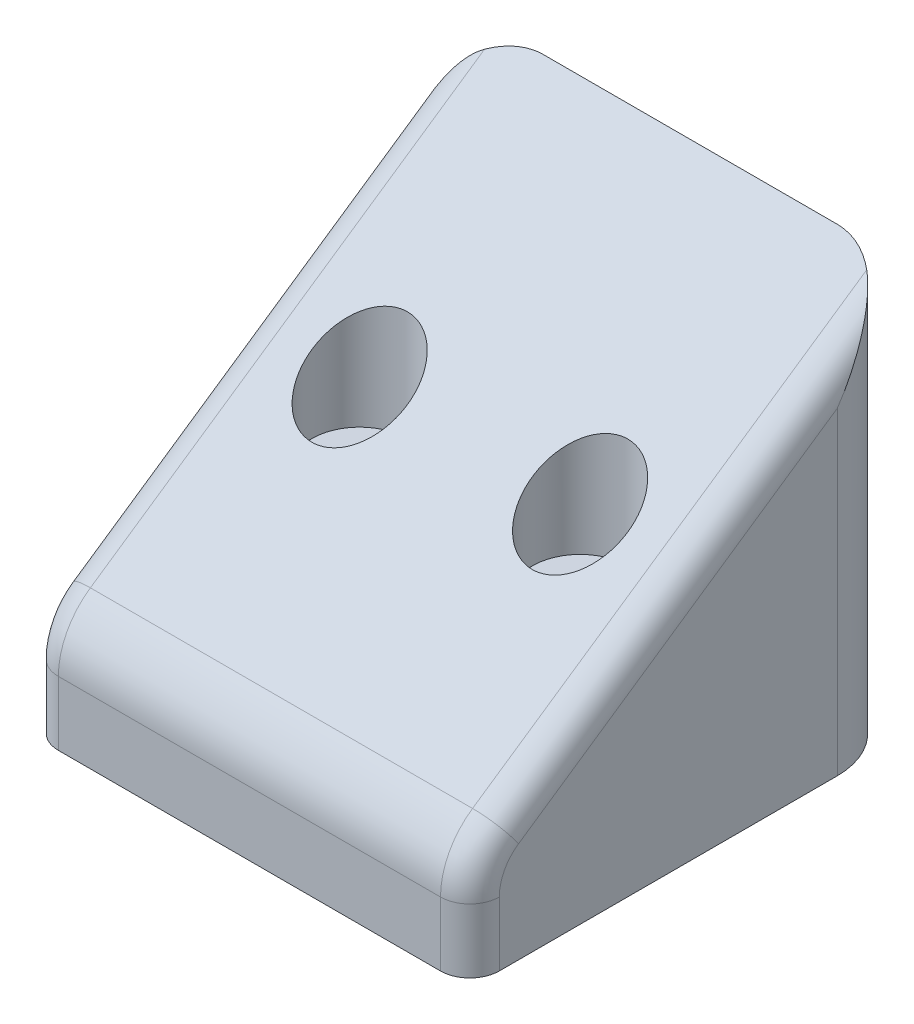
SolidWorks part; units mm, degrees
ref_plane "Спереди" through (0, 0, 0) normal (0, 0, 1) x (1, 0, 0)
ref_plane "Сверху" through (0, 0, 0) normal (0, 1, 0) x (1, 0, 0)
ref_plane "Справа" through (0, 0, 0) normal (1, 0, 0) x (0, 0, -1)
sketch "Sketch1" plane through (0, 0, 0) normal (0, 0, 1) x (1, 0, 0)
  line L0 (-15, 13.75) -> (15, -13.75) construction
  line L1 (-15, -13.75) -> (15, -13.75)
  line L2 (-15, -13.75) -> (-15, 13.75)
  line L3 (-15, 13.75) -> (15, 13.75)
  line L4 (15, -13.75) -> (15, 13.75)
  line L5 (-15, -13.75) -> (15, 13.75) construction
  point P4 (0, 0)
  dimension "D1" = 27.5
  dimension "D2" = 30
extrude "Extrude1" add sketch "Sketch1" along normal blind 30
sketch "Sketch3" plane through (15, 0, 0) normal (1, 0, 0) x (0, 0, -1)
  line L0 (-30, -6.75) -> (-30, 13.75)
  line L1 (-30, -13.75) -> (-30, 13.75) construction
  line L2 (-30, 13.75) -> (0, 13.75)
  line L3 (0, 13.75) -> (-30, -6.75)
  line L4 (-30, 13.75) -> (0, 13.75) construction
  dimension "D1" = 7
extrude "Extrude3" cut sketch "Sketch3" against normal through all
ref_plane "Plane1" through (0, 13.75, 0) normal (0, 1, 0) x (1, 0, 0)
sketch "Sketch7" plane through (0, 0, 0) normal (0, 0, -1) x (-1, 0, 0)
  line L0 (0, -13.75) -> (0, 13.75) construction
  line L1 (15, -13.75) -> (-15, -13.75) construction
  line L2 (16.5, 13.75) -> (-16.5, 13.75) construction
  circle A0 centre (-4.95, 3.65) radius 1.25
  circle A1 centre (4.95, 3.65) radius 1.25
  circle A2 centre (4.95, -6.25) radius 1.25
  circle A3 centre (-4.95, -6.25) radius 1.25
  dimension "D1" = 2
  dimension "D7" = 2.5
  dimension "D3" = 4.95
  dimension "D4" = 7.5
  dimension "D5" = 9.9
  dimension "D6" = 9.9
  dimension "D2" = 2
extrude "отверстия под саморезы " cut sketch "Sketch7" against normal blind 11
sketch "Sketch8" plane through (0, 13.75, 0) normal (0, 1, 0) x (1, 0, 0)
  line L0 (0, -30) -> (0, 0) construction
  line L1 (-15, -30) -> (15, -30) construction
  line L2 (15, 0) -> (-15, 0) construction
  circle A0 centre (-7.5, -15) radius 3.25
  circle A1 centre (7.5, -15) radius 3.25
  dimension "D1" = 6.5
  dimension "D2" = 15
  dimension "D3" = 15
extrude "Extrude8" cut sketch "Sketch8" against normal offset from surface (15.5 mm away) 12 up to face at (0, -13.75, 15)
sketch "Sketch9" plane through (0, 13.75, 0) normal (0, 1, 0) x (1, 0, 0)
  line L0 (0, 0) -> (0, -30) construction
  line L1 (-15, -30) -> (15, -30) construction
  circle A0 centre (-7.5, -15) radius 1.5
  circle A1 centre (7.5, -15) radius 1.5
  dimension "D1" = 3
extrude "Extrude9" cut sketch "Sketch9" against normal through all and the other way through all
fillet "Fillet1" radius 5 3 edges at (-15, 0, 0) (15, 0, 0) (0, -6.75, 30)
fillet "Fillet3" radius 2 9 edges at (15, -11.5696, 30) (15, -7.0552, 29.4218) (-15, -11.5696, 30) (-15, -7.0552, 29.4218) (-15, 2.5362, 16.4105) (-13.5355, 12.7493, 1.4645) (0, 13.75, 0) (13.5355, 12.7493, 1.4645) (15, 2.5362, 16.4105) tangent propagation no
